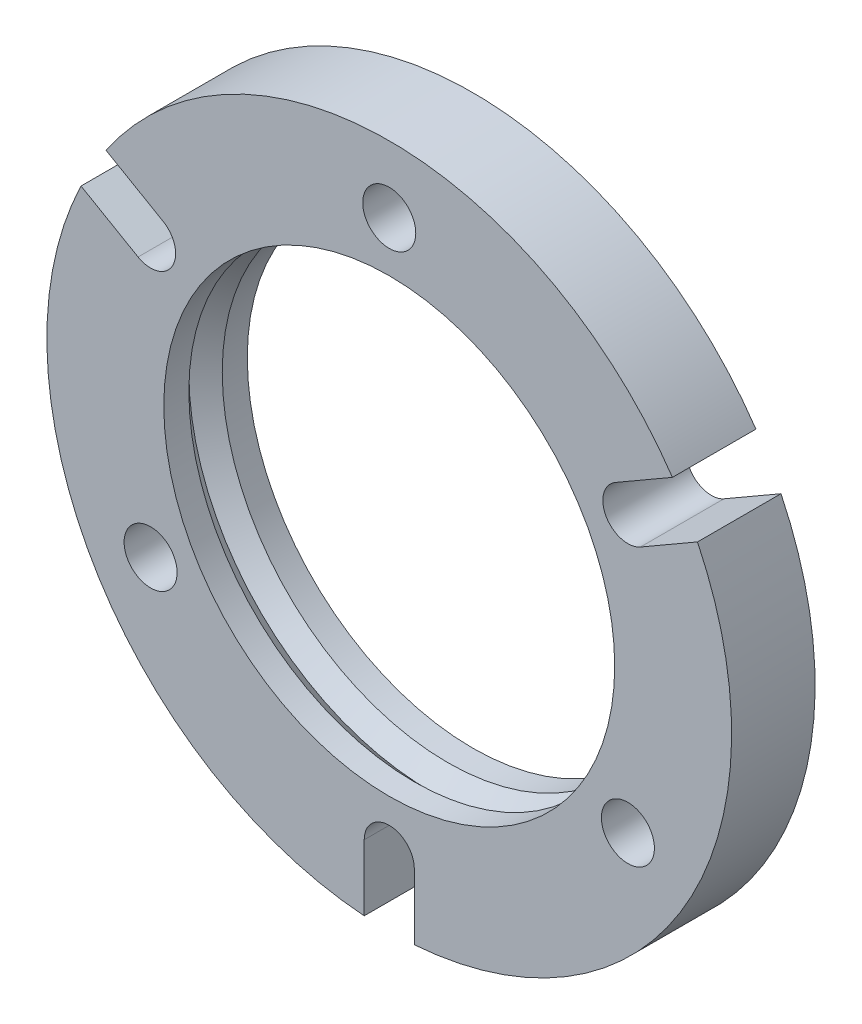
SolidWorks part; units mm, degrees
material "Polyetheretherketone (PEEK)"
ref_plane "Front Plane" through (0, 0, 0) normal (0, 0, 1) x (1, 0, 0)
ref_plane "Top Plane" through (0, 0, 0) normal (0, 1, 0) x (1, 0, 0)
ref_plane "Right Plane" through (0, 0, 0) normal (1, 0, 0) x (0, 0, -1)
sketch "Sketch1" plane through (0, 0, 0) normal (0, 0, 1) x (1, 0, 0)
  circle A0 centre (0, 0) radius 20.5
  circle A1 centre (0, 0) radius 13.5
  circle A2 centre (0, 16.5) radius 1.5875
  circle A3 centre (14.2894, -8.25) radius 1.5875
  circle A4 centre (-14.2894, -8.25) radius 1.5875
  circle A5 centre (0, 0) radius 16.5 construction
  dimension "D1" = 27
  dimension "D2" = 3.175
  dimension "D4" = 41
  dimension "D3" = 33
extrude "Extrude1" add sketch "Sketch1" along normal blind 5
sketch "Sketch2" plane through (0, 0, 5) normal (0, 0, 1) x (1, 0, 0)
  line L0 (1.5, -16.5) -> (1.5, -20.445)
  line L1 (-1.5, -16.5) -> (-1.5, -20.445)
  circle A0 centre (0, 0) radius 16.5 construction
  circle A1 centre (0, 0) radius 20.5
  circle A2 centre (0, 0) radius 20.5
  circle A3 centre (0, -16.5) radius 1.5
  circle M4 centre (0, 0) radius 20.5
  dimension "D2" = 3
  dimension "D1" = 0
extrude "Cut-Extrude1" cut sketch "Sketch2" against normal through all contours A3 L1 L0 M4 | A3 region at (0, -16.5, 5) region at (0, -19.06, 5)
sketch "Sketch3" plane through (0, 0, 0) normal (0, 1, 0) x (1, 0, 0)
  line L0 (0, -5) -> (0, 0) construction
  line L1 (-13.5, -5) -> (13.5, -5) construction
  line L2 (0, -5) -> (-9, -5) construction
  line L3 (-20.5, -5) -> (20.5, -5) construction
  line L4 (-9, -5) -> (-9, 0)
  line L5 (13.5, 0) -> (-13.5, 0) construction
  line L6 (20.5, 0) -> (-20.5, 0) construction
  line L7 (-12.4314, -5) -> (-9, -5)
  line L9 (0, 0) -> (0, 5.2553) construction
  line L10 (0, 5.2553) -> (-20.5, 5.2553)
  line L11 (-20.5, 5.2553) -> (-20.5, 0)
  line L12 (-20.5, 0) -> (0, 0)
  line L13 (-9, 0) -> (-9, 5.2553)
  line L14 (-9, 5.2553) -> (-12.4314, -5)
  line L15 (-15.8769, -5) -> (-12.7019, -5) construction
  dimension "D1" = 9
  dimension "D2" = 18.5
  dimension "D3" = 5.2553
revolve "Cut-Revolve1" [suppressed] cut sketch "Sketch3" angle 360 about L0
sketch "Sketch4" plane through (0, 0, 0) normal (0, 1, 0) x (1, 0, 0)
  line L0 (0, 0) -> (0, -5) construction
  line L1 (-13.5, -5) -> (13.5, -5) construction
  line L2 (-13.5, 0) -> (-13.5, -5)
  line L3 (13.5, 0) -> (-13.5, 0) construction
  line L4 (-12.7019, 0) -> (-15.8769, 0) construction
  line L5 (0, -2.5) -> (-13.5, -2.5) construction
  line L6 (-13.5, -2.5) -> (-14.5, -2.5)
  line L7 (-14.5, -2.5) -> (-13.5, -1.5)
  line L8 (-14.5, -2.5) -> (-13.5, -3.5)
  dimension "D1" = 13.5
  dimension "D2" = 45
  dimension "D3" = 1
revolve "Cut-Revolve3" cut sketch "Sketch4" angle 360 about L0 region at (-13.8333, 0, 2.1667) region at (-13.8333, 0, 2.8333)
ref_axis "Axis1" through (0, 0, 5) along (0, 0, -1)
pattern_circular "CirPattern1" count 3 over 360 about axis through (0, 0, 5) along (0, 0, -1) of "Cut-Extrude1"
